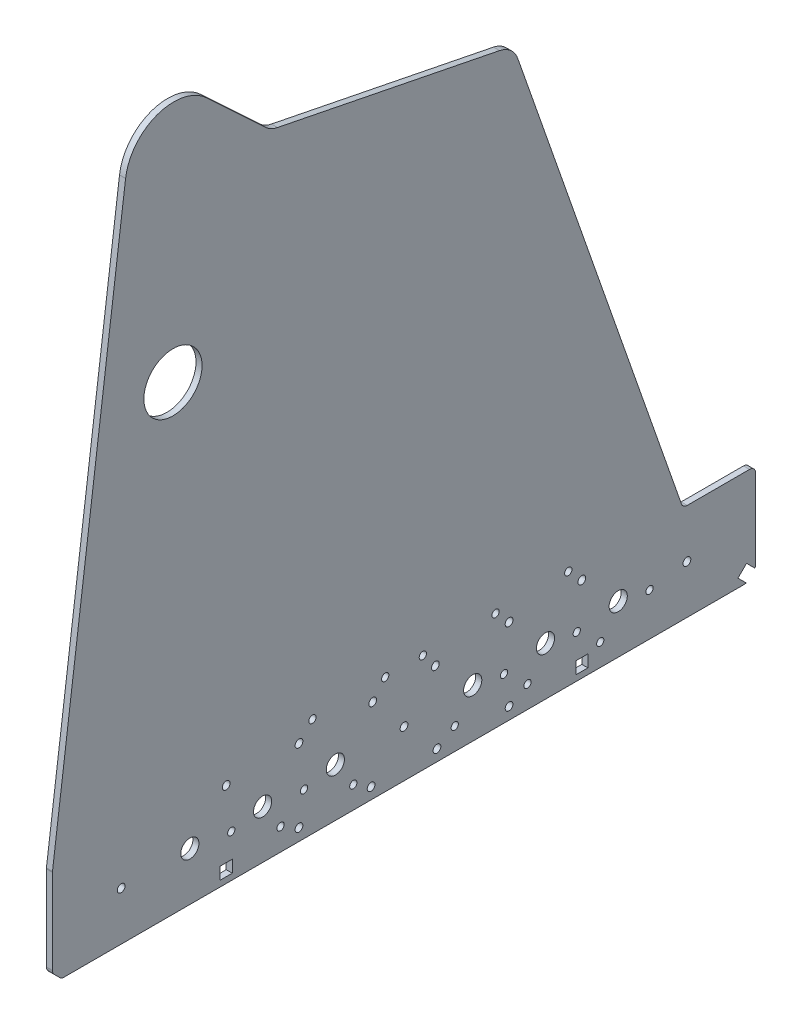
SolidWorks part; units mm, degrees
ref_plane "Front Plane" through (0, 0, 0) normal (0, 0, 1) x (1, 0, 0)
ref_plane "Top Plane" through (0, 0, 0) normal (0, 1, 0) x (1, 0, 0)
ref_plane "Right Plane" through (0, 0, 0) normal (1, 0, 0) x (0, 0, -1)
sketch "Sketch1" plane through (0, 0, 0) normal (1, 0, 0) x (0, 0, -1)
  line L0 (-184.15, -24.6062) -> (184.15, -24.6062)
  line L1 (184.15, -24.6062) -> (184.15, 26.1938)
  line L2 (184.15, 26.1938) -> (146.05, 26.1937)
  line L3 (146.05, 26.1937) -> (57.15, 280.1938)
  line L5 (-145.839, 321.5609) -> (-184.15, 26.1938)
  line L6 (-184.15, 26.1938) -> (-184.15, -24.6062)
  line L7 (-184.15, 350.0437) -> (184.15, 350.0437) construction
  line L8 (57.15, 280.1938) -> (-69.85, 305.5938)
  line L9 (-69.85, 305.5938) -> (-103.3099, 336.854)
  arc A0 (-103.3099, 336.854) -> (-145.839, 321.5609) centre (-120.65, 318.2937) ccw
  point P8 (0, -24.6062)
  dimension "D1" = 368.3
  dimension "D7" = 25.4
  dimension "D2" = 50.8
  dimension "D3" = 38.1
  dimension "D4" = 24.6062
  dimension "D5" = 374.65
  dimension "D6" = 304.8
  dimension "D8" = 342.9
  dimension "D9" = 127
  dimension "D10" = 304.8
  dimension "D11" = 25.4
  dimension "D12" = 127
extrude "Boss-Extrude1" add sketch "Sketch1" along normal blind 3.175
chamfer "Chamfer1" distance 4.7625 angle 45 2 edges at (1.5875, -24.6062, 184.15) (1.5875, -24.6062, -184.15)
fillet "Fillet1" radius 12.7 2 edges at (1.5875, 305.5938, 69.85) (1.5875, 280.1938, -57.15)
fillet "Fillet2" radius 3.175 3 edges at (1.5875, 26.1938, 184.15) (1.5875, 26.1938, -184.15) (1.5875, 26.1937, -146.05)
fillet "Fillet3" radius 3.175 4 edges at (1.5875, -19.8438, -184.15) (1.5875, -24.6062, -179.3875) (1.5875, -19.8437, 184.15) (1.5875, -24.6062, 179.3875)
sketch "Sketch16" plane through (3.175, 0, 0) normal (1, 0, 0) x (0, 0, -1)
  circle A0 centre (112.1746, 0.7937) radius 4.7625
  circle A1 centre (74.0746, 0.7937) radius 4.7625
  circle A2 centre (35.9746, 0.7937) radius 4.7625
  circle A3 centre (-35.9746, 0.7938) radius 4.7625
  circle A4 centre (-74.0746, 0.7938) radius 4.7625
  circle A5 centre (-112.1746, 0.7937) radius 4.7625
  dimension "D1" = 9.525
  dimension "D2" = 9.525
extrude "Cut-Extrude1" cut sketch "Sketch16" against normal up to next
sketch "Sketch25" plane through (3.175, 0, 0) normal (1, 0, 0) x (0, 0, -1)
  circle A0 centre (102.7672, -13.0003) radius 1.905 construction
  circle A1 centre (86.0486, 27.3622) radius 1.905 construction
  circle A2 centre (128.5804, -2.3081) radius 1.905 construction
  circle A3 centre (102.7672, -13.0003) radius 1.905
  circle A4 centre (86.0486, 27.3622) radius 1.905
  circle A5 centre (128.5804, -2.3081) radius 1.905
  circle A6 centre (64.6672, -13.0003) radius 1.905 construction
  circle A8 centre (-9.8486, 27.3622) radius 1.905 construction
  circle A10 centre (-47.9486, 27.3622) radius 1.905 construction
  circle A11 centre (-90.4804, -2.3081) radius 1.905 construction
  circle A12 centre (-64.6672, -13.0003) radius 1.905 construction
  circle A14 centre (-52.3804, -2.3081) radius 1.905 construction
  circle A15 centre (-26.5672, -13.0003) radius 1.905 construction
  circle A16 centre (9.8486, 27.3622) radius 1.905 construction
  circle A17 centre (26.5672, -13.0003) radius 1.905 construction
  circle A18 centre (47.9486, 27.3622) radius 1.905 construction
  circle A19 centre (52.3804, -2.3081) radius 1.905 construction
  circle A20 centre (90.4804, -2.3081) radius 1.905 construction
  circle A21 centre (-9.8486, 27.3622) radius 1.905
  circle A23 centre (-47.9486, 27.3622) radius 1.905
  circle A24 centre (-90.4804, -2.3081) radius 1.905
  circle A25 centre (-64.6672, -13.0003) radius 1.905
  circle A27 centre (-52.3804, -2.3081) radius 1.905
  circle A28 centre (-26.5672, -13.0003) radius 1.905
  circle A29 centre (9.8486, 27.3622) radius 1.905
  circle A30 centre (26.5672, -13.0003) radius 1.905
  circle A31 centre (47.9486, 27.3622) radius 1.905
  circle A32 centre (64.6672, -13.0003) radius 1.905
  circle A33 centre (52.3804, -2.3081) radius 1.905
  circle A34 centre (90.4804, -2.3081) radius 1.905
extrude "Cut-Extrude4" cut sketch "Sketch25" against normal up to next
sketch "Sketch23" plane through (3.175, 0, 0) normal (1, 0, 0) x (0, 0, -1)
  point P0 (-55.0246, -18.3223)
  point P3 (-55.0246, 19.9098)
  point P6 (-93.1246, 19.9098)
  point P9 (-17.2515, -18.6426)
  point P12 (-16.4124, 19.3854)
  point P15 (16.4124, 19.3854)
  point P18 (17.2515, -18.6426)
  point P21 (55.0246, -18.3223)
  point P27 (93.1246, 19.9098)
  point P30 (55.0246, 19.9098)
hole_wizard "#8 (0.16) Diameter Hole1" positions "Sketch23" profile "Sketch24" hole size "#8" standard "ANSI Inch" end condition up to next
sketch "Sketch24" plane through (3.175, -18.3223, 55.0246) normal (0, 1, 0) x (0, 0, -1)
  line L0 (0, 0) -> (0, 3.175)
  line L1 (0, 3.175) -> (2.032, 3.175)
  line L2 (2.032, 3.175) -> (2.032, 0)
  line L5 (2.032, 0) -> (0, 0)
  line L11 (0, -6.35) -> (0, 107.95) construction
  dimension "Thru Hole Dia." = 4.064
  dimension "Thru Hole Depth" = 3.175
sketch "Sketch22" plane through (3.175, 0, 0) normal (1, 0, 0) x (0, 0, -1)
  line L0 (-96.2996, -15.1473) -> (-89.9496, -15.1473) construction
  line L1 (-96.2996, -15.1473) -> (-89.9496, -15.1473)
  line L2 (-96.2996, -15.1473) -> (-96.2996, -21.4973)
  line L3 (-96.2996, -21.4973) -> (-89.9496, -21.4973)
  line L4 (-89.9496, -15.1473) -> (-89.9496, -21.4973)
  line L5 (-96.2996, -15.1473) -> (-89.9496, -21.4973) construction
  line L6 (-96.2996, -21.4973) -> (-89.9496, -15.1473) construction
  line L7 (-89.9496, -15.1473) -> (-89.9496, -19.8734) construction
  line L77 (179.3875, -24.6062) -> (183.8776, -20.1161)
  line L78 (179.3875, -24.6062) -> (174.8974, -20.1161)
  line L79 (183.8776, -20.1161) -> (179.3875, -15.626)
  line L80 (174.8974, -20.1161) -> (179.3875, -15.626)
  line L81 (180.3174, -23.6763) -> (183.2201, -20.7737) construction
  line L82 (-178.0724, -24.6062) -> (178.0724, -24.6062) construction
  line L84 (89.9496, -21.4973) -> (96.2996, -21.4973)
  line L85 (89.9496, -21.4973) -> (89.9496, -15.1473)
  line L86 (89.9496, -15.1473) -> (96.2996, -15.1473)
  line L87 (96.2996, -21.4973) -> (96.2996, -15.1473)
  line L88 (89.9496, -21.4973) -> (96.2996, -15.1473) construction
  line L89 (89.9496, -15.1473) -> (96.2996, -21.4973) construction
  point P0 (-93.1246, -18.3223)
  point P19 (93.1246, -18.3223)
  dimension "D1" = 6.35
  dimension "D2" = 6.35
extrude "Cut-Extrude3" cut sketch "Sketch22" against normal up to next
sketch "Sketch21" plane through (3.175, 0, 0) normal (1, 0, 0) x (0, 0, -1)
  circle A0 centre (-148.1579, 0.7937) radius 2.032
  circle A2 centre (0, 0) radius 2.032
  circle A3 centre (148.1579, 0.7938) radius 2.032
  dimension "D1" = 4.064
extrude "Cut-Extrude2" cut sketch "Sketch21" against normal up to next
sketch "Sketch26" plane through (3.175, 0, 0) normal (1, 0, 0) x (0, 0, -1)
  line L0 (-145.839, 321.5609) -> (-184.1236, 26.3971) construction
  line L1 (-178.0724, -24.6062) -> (178.0724, -24.6062) construction
  circle A0 centre (-121.0218, 216.6937) radius 15.24
  dimension "D1" = 30.48
  dimension "D2" = 38.1
  dimension "D3" = 241.3
extrude "Cut-Extrude5" cut sketch "Sketch26" against normal through all
